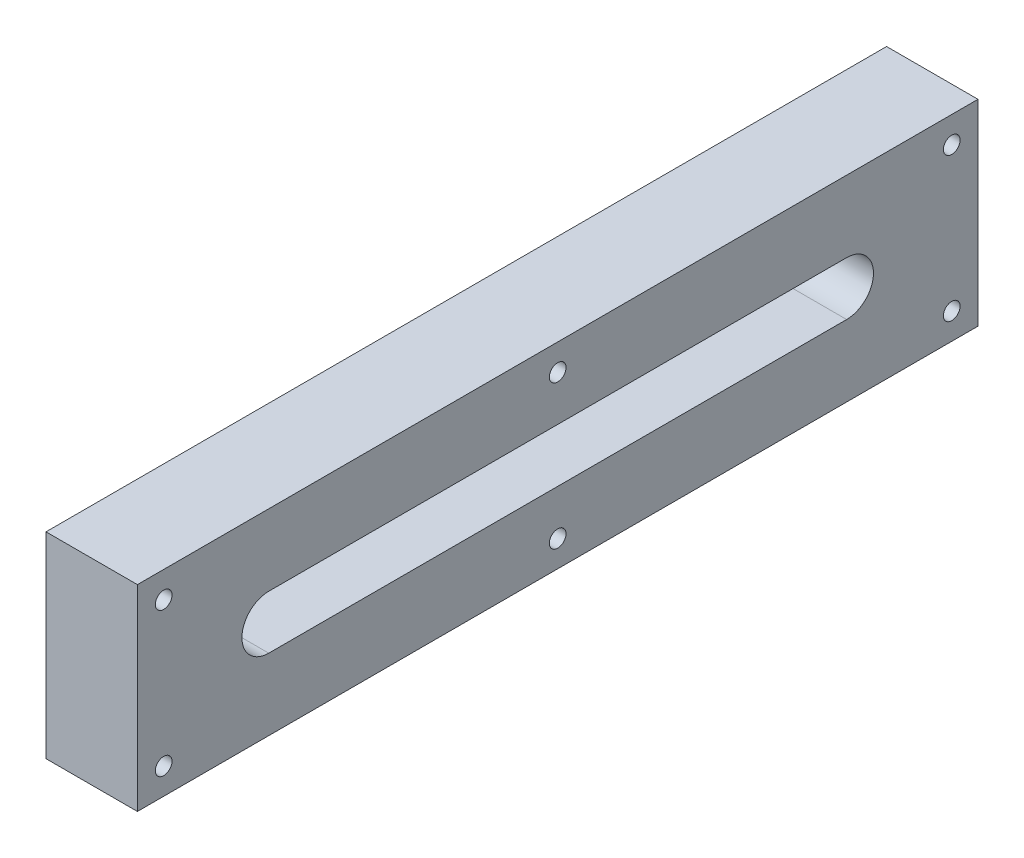
SolidWorks part; units mm, degrees
material "Delrin 2700 NC010, Low Viscosity Acetal Copolymer (SS)"
ref_plane "Front" through (0, 0, 0) normal (0, 0, 1) x (1, 0, 0)
ref_plane "Top" through (0, 0, 0) normal (0, 1, 0) x (1, 0, 0)
ref_plane "Right" through (0, 0, 0) normal (1, 0, 0) x (0, 0, -1)
sketch "Sketch1" plane through (0, 0, 0) normal (1, 0, 0) x (0, 0, -1)
  line L0 (-69.85, 0) -> (69.85, 0) construction
  line L1 (101.6, -23.749) -> (-101.6, -23.749)
  line L2 (101.6, -23.749) -> (101.6, 23.749)
  line L3 (101.6, 23.749) -> (-101.6, 23.749)
  line L4 (-101.6, -23.749) -> (-101.6, 23.749)
  line L5 (101.6, -23.749) -> (-101.6, 23.749) construction
  line L6 (101.6, 23.749) -> (-101.6, -23.749) construction
  line L7 (-69.85, 2.5) -> (69.85, 2.5)
  line L8 (-69.85, -2.5) -> (69.85, -2.5)
  arc A0 (-69.85, 2.5) -> (-69.85, -2.5) centre (-69.85, 0) ccw
  arc A1 (69.85, -2.5) -> (69.85, 2.5) centre (69.85, 0) ccw
  point P0 (0, 0)
  point P8 (0, 0)
  dimension "D4" = 5
  dimension "D1" = 139.7
  dimension "D2" = 203.2
  dimension "D3" = 47.498
extrude "Boss-Extrude1" add sketch "Sketch1" along normal blind 22.098
sketch "Sketch2" plane through (22.098, 0, 0) normal (1, 0, 0) x (0, 0, -1)
  line L0 (-69.85, 0) -> (69.85, 0) construction
  line L1 (-69.85, 6.4798) -> (69.85, 6.4798)
  line L2 (-69.85, -6.4798) -> (69.85, -6.4798)
  line L3 (69.85, 2.5) -> (-69.85, 2.5) construction
  arc A0 (-69.85, 6.4798) -> (-69.85, -6.4798) centre (-69.85, 0) ccw
  arc A1 (69.85, -6.4798) -> (69.85, 6.4798) centre (69.85, 0) ccw
  point P2 (0, 0)
  dimension "D2" = 12.9595
extrude "Cut-Extrude1" cut sketch "Sketch2" against normal blind 17.78
hole_wizard "#10-32 Tapped Hole1" positions "Sketch3" profile "Sketch4" tap size "#10-32" standard "ANSI Inch" end condition through all
sketch "Sketch3" plane through (22.098, 0, 0) normal (1, 0, 0) x (0, 0, -1)
  line L0 (-95.25, 17.399) -> (0, 17.399) construction
  line L1 (0, 17.399) -> (95.25, 17.399) construction
  line L3 (-95.25, 23.749) -> (-95.25, 17.399) construction
  line L4 (101.6, 23.749) -> (-101.6, 23.749) construction
  line L5 (-95.25, 17.399) -> (-95.25, -17.399) construction
  line L6 (-95.25, -17.399) -> (-95.25, -23.749) construction
  line L7 (-101.6, -23.749) -> (101.6, -23.749) construction
  line L8 (-101.6, 23.749) -> (-101.6, -23.749) construction
  point P0 (-95.25, 17.399)
  point P2 (-95.25, -17.399)
  point P4 (0, -17.399)
  point P6 (95.25, -17.399)
  point P8 (95.25, 17.399)
  point P10 (0, 17.399)
  dimension "D1" = 6.35
  dimension "D2" = 6.35
sketch "Sketch4" plane through (22.098, 17.399, 95.25) normal (0, 1, 0) x (0, 0, -1)
  line L0 (0, 0) -> (0, 22.098)
  line L1 (0, 22.098) -> (2.0193, 22.098)
  line L2 (2.0193, 22.098) -> (2.0193, 0)
  line L5 (2.0193, 0) -> (0, 0)
  line L11 (0, -6.35) -> (0, 107.95) construction
  dimension "Thru Tap Drill Dia." = 4.0386
  dimension "Thru Tap Drill Depth" = 22.098
cosmetic thread "Hole Thread1" parameters "D2"=4.826
cosmetic thread "Hole Thread2" parameters "D2"=4.826
cosmetic thread "Hole Thread3" parameters "D2"=4.826
cosmetic thread "Hole Thread4" parameters "D2"=4.826
cosmetic thread "Hole Thread5" parameters "D2"=4.826
cosmetic thread "Hole Thread6" parameters "D2"=4.826
